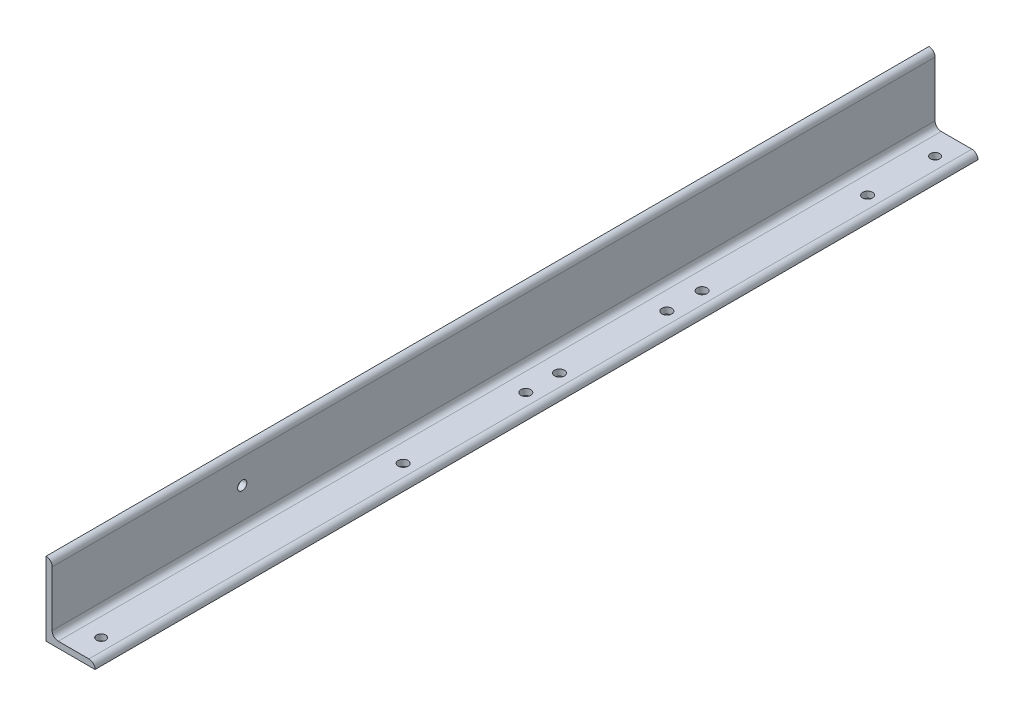
SolidWorks part; units mm, degrees
ref_plane "Front Plane" through (0, 0, 0) normal (0, 0, 1) x (1, 0, 0)
ref_plane "Top Plane" through (0, 0, 0) normal (0, 1, 0) x (1, 0, 0)
ref_plane "Right Plane" through (0, 0, 0) normal (1, 0, 0) x (0, 0, -1)
sketch "Sketch1" plane through (0, 0, 0) normal (0, 0, 1) x (1, 0, 0)
  line L0 (0, 0) -> (0, 152.4)
  line L1 (0, 152.4) -> (0.0051, 152.4)
  line L2 (12.7, 139.7051) -> (12.7, 25.4)
  line L3 (25.4, 12.7) -> (88.9051, 12.7)
  line L4 (101.6, 0.0051) -> (101.6, 0)
  line L5 (101.6, 0) -> (0, 0)
  arc A0 (101.6, 0.0051) -> (88.9051, 12.7) centre (88.9051, 0.0051) ccw
  arc A1 (0.0051, 152.4) -> (12.7, 139.7051) centre (0.0051, 139.7051) cw
  arc A2 (25.4, 12.7) -> (12.7, 25.4) centre (25.4, 25.4) cw
  circle A3 centre (0, 0) radius 12.7 construction
  dimension "D2" = 0.0051
  dimension "Radius_1" = 12.7
  dimension "Radius_2" = 12.7
  dimension "D1" = 12.7
  dimension "V_leg" = 152.4
  dimension "H_leg" = 101.6
  dimension "Thickness" = 12.7
  dimension "Flat_wid" = 0.0051
extrude "Boss-Extrude1" add sketch "Sketch1" along normal mid plane 1828.8
sketch "Sketch3" plane through (0, 12.7, 0) normal (0, 1, 0) x (1, 0, 0)
  line L0 (63.5, -964.9914) -> (63.5, 988.9202) construction
  line L1 (101.6, -914.4) -> (101.6, 914.4) construction
  line L2 (88.9051, -914.4) -> (25.4, -914.4) construction
  line L3 (88.9051, 914.4) -> (25.4, 914.4) construction
  circle A0 centre (63.5, -863.6) radius 9.525
  circle A1 centre (63.5, 863.6) radius 9.525
  circle A2 centre (63.5, 15.875) radius 10.3187
  circle A4 centre (63.5, 723.9) radius 10.3187
  circle A5 centre (63.5, 381) radius 10.3188
  circle A6 centre (63.5, -238.125) radius 10.3187
  circle A7 centre (63.5, 307.975) radius 10.3188
  circle A8 centre (63.5, 85.725) radius 10.3188
  dimension "D3" = 50.8
  dimension "D4" = 69.85
  dimension "D5" = 254
  dimension "D6" = 190.5
  dimension "D7" = 342.9
  dimension "D9" = 20.6375
  dimension "D10" = 222.25
  dimension "D11" = 606.425
  dimension "D1" = 38.1
  dimension "D2" = 50.8
extrude "Cut-Extrude2" cut sketch "Sketch3" against normal up to next
hole_wizard "3/4 (0.75) Diameter Hole1" positions "Sketch5" profile "Sketch4" hole size "3/4" standard "Ansi Inch" end condition up to next
sketch "Sketch5" plane through (12.7, 0, 0) normal (1, 0, 0) x (0, 0, -1)
  line L0 (-914.4, 25.4) -> (-914.4, 139.7051) construction
  line L1 (-914.4, 152.4) -> (914.4, 152.4) construction
  point P0 (-520.7, 88.9)
  dimension "D1" = 393.7
  dimension "D2" = 63.5
sketch "Sketch4" plane through (12.7, 88.9, 520.7) normal (0, 1, 0) x (0, 0, -1)
  line L0 (0, 0) -> (0, 12.7)
  line L1 (0, 12.7) -> (9.525, 12.7)
  line L2 (9.525, 12.7) -> (9.525, 0)
  line L5 (9.525, 0) -> (0, 0)
  line L11 (0, -6.35) -> (0, 107.95) construction
  dimension "Thru Hole Dia." = 19.05
  dimension "Thru Hole Depth" = 12.7
equation "\"D3@Sketch3\" = \"D2@Sketch3\""
